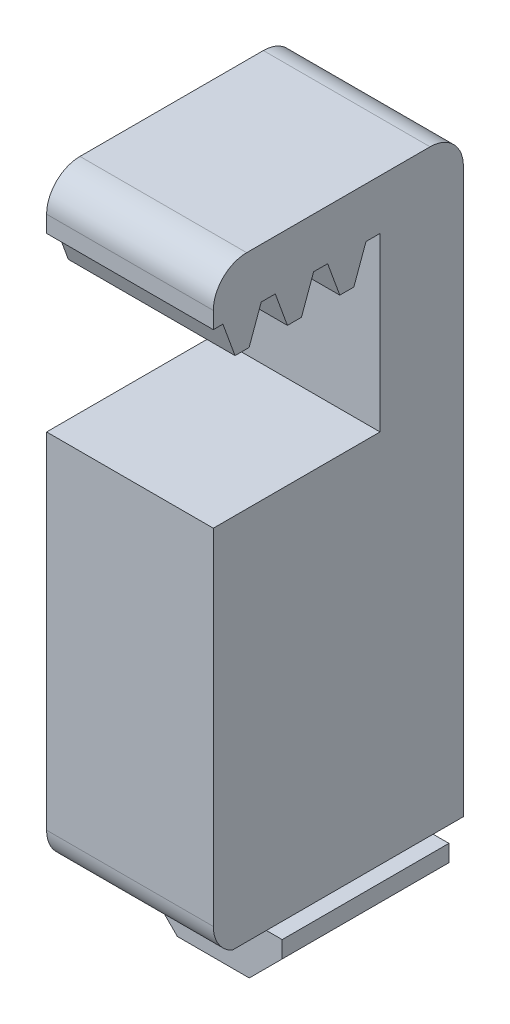
SolidWorks part; units mm, degrees
material "PLA Grey"
ref_plane "Front Plane" through (0, 0, 0) normal (0, 0, 1) x (1, 0, 0)
ref_plane "Top Plane" through (0, 0, 0) normal (0, 1, 0) x (1, 0, 0)
ref_plane "Right Plane" through (0, 0, 0) normal (1, 0, 0) x (0, 0, -1)
sketch "Sketch1" plane through (0, 0, 0) normal (1, 0, 0) x (0, 0, -1)
  line L0 (6.35, 0) -> (6.35, -6.096)
  line L1 (0, 45.72) -> (12.7, 45.72)
  line L2 (0, 45.72) -> (0, 39.37)
  line L3 (0, 39.37) -> (12.7, 39.37)
  line L5 (12.7, 45.72) -> (19.05, 45.72)
  line L6 (12.7, 39.37) -> (12.7, 29.21)
  line L7 (6.35, -6.096) -> (19.05, -6.096)
  line L8 (19.05, 45.72) -> (19.05, -6.096)
  line L9 (12.7, 29.21) -> (0, 29.21)
  line L11 (6.35, 0) -> (0, 0)
  line L12 (0, 29.21) -> (0, 0)
  line L13 (12.7, 29.21) -> (-1206.5, 29.21) construction
  dimension "D1" = 6.35
  dimension "D2" = 12.7
  dimension "D3" = 10.16
  dimension "D4" = 6.35
  dimension "D5" = 12.7
  dimension "D6" = 6.096
extrude "Boss-Extrude1" add sketch "Sketch1" along normal mid plane 12.7
sketch "Sketch2" plane through (6.35, 0, 0) normal (1, 0, 0) x (0, 0, -1)
  line L0 (3.6499, 41.91) -> (4.7203, 41.91) construction
  line L1 (5.6948, 39.2327) -> (4.7203, 41.91) construction
  line L2 (6.4261, 39.0652) -> (5.934, 39.0652) construction
  line L3 (7.6397, 41.91) -> (6.6653, 39.2327) construction
  line L4 (7.6397, 41.91) -> (8.7102, 41.91) construction
  line L5 (9.6846, 39.2327) -> (8.7102, 41.91) construction
  line L6 (10.4159, 39.0652) -> (9.9238, 39.0652) construction
  line L7 (11.6296, 41.91) -> (10.6551, 39.2327) construction
  line L8 (11.6296, 41.91) -> (12.7, 41.91) construction
  line L9 (3.6499, 41.91) -> (4.7203, 41.91)
  line L10 (5.6948, 39.2327) -> (4.7203, 41.91)
  line L11 (6.4261, 39.0652) -> (5.934, 39.0652)
  line L12 (7.6397, 41.91) -> (6.6653, 39.2327)
  line L13 (7.6397, 41.91) -> (8.7102, 41.91)
  line L14 (9.6846, 39.2327) -> (8.7102, 41.91)
  line L15 (10.4159, 39.0652) -> (9.9238, 39.0652)
  line L16 (11.6296, 41.91) -> (10.6551, 39.2327)
  line L17 (11.6296, 41.91) -> (12.7, 41.91)
  line L18 (12.7, 41.91) -> (12.7, 29.21)
  line L19 (12.7, 39.37) -> (12.7, 29.21) construction
  line L20 (12.7, 29.21) -> (3.6499, 29.21)
  line L21 (3.6499, 29.21) -> (3.6499, 41.91)
  line L22 (12.7, 29.21) -> (0, 29.21) construction
  arc A0 (5.6948, 39.2327) -> (5.934, 39.0652) centre (5.934, 39.3198) ccw construction
  arc A1 (6.4261, 39.0652) -> (6.6653, 39.2327) centre (6.4261, 39.3198) ccw construction
  arc A2 (9.6846, 39.2327) -> (9.9238, 39.0652) centre (9.9238, 39.3198) ccw construction
  arc A3 (10.4159, 39.0652) -> (10.6551, 39.2327) centre (10.4159, 39.3198) ccw construction
  arc A4 (5.6948, 39.2327) -> (5.934, 39.0652) centre (5.934, 39.3198) ccw
  arc A5 (6.4261, 39.0652) -> (6.6653, 39.2327) centre (6.4261, 39.3198) ccw
  arc A6 (9.6846, 39.2327) -> (9.9238, 39.0652) centre (9.9238, 39.3198) ccw
  arc A7 (10.4159, 39.0652) -> (10.6551, 39.2327) centre (10.4159, 39.3198) ccw
extrude "Cut-Extrude1" cut sketch "Sketch2" against normal through all
pattern_linear "LPattern1" count 10 spacing 3.9898 along (0, 0, 1) of "Cut-Extrude1"
sketch "Sketch3" plane through (0, 0, -19.05) normal (0, 0, -1) x (-1, 0, 0)
  line L0 (-6.35, -6.096) -> (-2.8393, -6.1)
  line L1 (2.8393, -6.1) -> (5.5, -3.4393) construction
  line L2 (5.5, -3.4393) -> (5.5, -1.8) construction
  line L3 (5.5, -1.8) -> (3.125, -1.8) construction
  line L4 (3.125, -1.8) -> (3.125, -1.455) construction
  line L5 (3.125, -1.455) -> (4.58, 0) construction
  line L6 (15.42, 0) -> (4.58, 0) construction
  line L7 (-4.58, 0) -> (-9.5, 0) construction
  line L8 (-3.125, -1.455) -> (-4.58, 0) construction
  line L9 (-3.125, -1.8) -> (-3.125, -1.455) construction
  line L10 (-5.5, -1.8) -> (-3.125, -1.8) construction
  line L11 (-5.5, -3.4393) -> (-5.5, -1.8) construction
  line L12 (-2.8393, -6.1) -> (-5.5, -3.4393) construction
  line L13 (2.8393, -6.1) -> (6.35, -6.096)
  line L15 (2.8393, -6.1) -> (5.5, -3.4393)
  line L16 (5.5, -3.4393) -> (5.5, -1.8)
  line L17 (5.5, -1.8) -> (3.125, -1.8)
  line L18 (3.125, -1.8) -> (3.125, -1.455)
  line L19 (3.125, -1.455) -> (4.58, 0)
  line L20 (15.42, 0) -> (4.58, 0)
  line L21 (-4.58, 0) -> (-9.5, 0)
  line L22 (-3.125, -1.455) -> (-4.58, 0)
  line L23 (-3.125, -1.8) -> (-3.125, -1.455)
  line L24 (-5.5, -1.8) -> (-3.125, -1.8)
  line L25 (-5.5, -3.4393) -> (-5.5, -1.8)
  line L26 (-2.8393, -6.1) -> (-5.5, -3.4393)
  line L29 (-9.5, 0) -> (-6.35, -6.096)
  line L32 (6.35, -6.096) -> (15.42, 0)
extrude "Cut-Extrude2" cut sketch "Sketch3" against normal through all
fillet "Fillet1" radius 2.54 3 edges at (0, 0, 0) (0, 45.72, 0) (0, 45.72, -19.05)
sketch "Sketch5" plane through (0, 0, -19.05) normal (0, 0, -1) x (-1, 0, 0)
  line L0 (6.35, 0) -> (4.58, 0) construction
  line L1 (4.58, 0) -> (3.125, -1.455) construction
  line L2 (3.125, -1.455) -> (3.125, -1.8) construction
  line L3 (3.125, -1.8) -> (5.5, -1.8) construction
  line L4 (5.5, -1.8) -> (5.5, -3.4393) construction
  line L5 (5.5, -3.4393) -> (2.8433, -6.096) construction
  line L6 (-2.8433, -6.096) -> (2.8433, -6.096) construction
  line L7 (-2.8433, -6.096) -> (-5.5, -3.4393) construction
  line L8 (-5.5, -3.4393) -> (-5.5, -1.8) construction
  line L9 (-5.5, -1.8) -> (-3.125, -1.8) construction
  line L10 (-3.125, -1.8) -> (-3.125, -1.455) construction
  line L11 (-3.125, -1.455) -> (-4.58, 0) construction
  line L12 (-4.58, 0) -> (-6.35, 0) construction
  line L13 (6.35, 0) -> (4.58, 0)
  line L14 (4.58, 0) -> (3.125, -1.455)
  line L15 (3.125, -1.455) -> (3.125, -1.8)
  line L16 (3.125, -1.8) -> (5.5, -1.8)
  line L17 (5.5, -1.8) -> (5.5, -3.4393)
  line L18 (5.5, -3.4393) -> (2.8433, -6.096)
  line L19 (-2.8433, -6.096) -> (2.8433, -6.096)
  line L20 (-2.8433, -6.096) -> (-5.5, -3.4393)
  line L21 (-5.5, -3.4393) -> (-5.5, -1.8)
  line L22 (-5.5, -1.8) -> (-3.125, -1.8)
  line L23 (-3.125, -1.8) -> (-3.125, -1.455)
  line L24 (-3.125, -1.455) -> (-4.58, 0)
  line L25 (-4.58, 0) -> (-6.35, 0)
  line L26 (6.35, 0.254) -> (4.4748, 0.254)
  line L27 (4.4748, 0.254) -> (2.871, -1.3498)
  line L28 (2.871, -1.3498) -> (2.871, -2.054)
  line L29 (2.871, -2.054) -> (5.246, -2.054)
  line L30 (5.246, -2.054) -> (5.246, -3.3341)
  line L31 (5.246, -3.3341) -> (2.7381, -5.842)
  line L32 (-2.7381, -5.842) -> (2.7381, -5.842)
  line L33 (-2.7381, -5.842) -> (-5.246, -3.3341)
  line L34 (-5.246, -3.3341) -> (-5.246, -2.054)
  line L35 (-5.246, -2.054) -> (-2.871, -2.054)
  line L36 (-2.871, -2.054) -> (-2.871, -1.3498)
  line L37 (-2.871, -1.3498) -> (-4.4748, 0.254)
  line L38 (-4.4748, 0.254) -> (-6.35, 0.254)
  line L39 (6.35, 0) -> (6.35, 0.254)
  line L40 (-6.35, 0) -> (-6.35, 0.254)
  dimension "D1" = 0.254
extrude "Cut-Extrude3" cut sketch "Sketch5" against normal through all
sketch "Sketch6" plane through (6.35, 0, 0) normal (1, 0, 0) x (0, 0, -1)
  line L0 (12.7, 41.91) -> (12.7, 29.21) construction
  line L1 (0, 29.21) -> (12.7, 29.21)
  line L2 (0, 29.21) -> (0, 28.8131)
  line L3 (0, 28.8131) -> (12.7, 28.8131)
  line L4 (12.7, 29.21) -> (12.7, 28.8131)
  dimension "D1" = 0.3969
extrude "Cut-Extrude4" cut sketch "Sketch6" against normal through all
sketch "Sketch7" [suppressed] plane through (6.35, 0, 0) normal (1, 0, 0) x (0, 0, -1)
  line L0 (19.05, 0.1984) -> (19.05, 42.926) construction
  line L1 (0, 28.8131) -> (19.05, 28.8131)
  line L2 (0, 28.8131) -> (0, 45.466)
  line L3 (0, 45.466) -> (19.05, 45.466)
  line L4 (19.05, 28.8131) -> (19.05, 45.466)
  line L5 (0, 28.8131) -> (19.05, 45.466) construction
  line L6 (0, 45.466) -> (19.05, 28.8131) construction
  line L7 (16.51, 45.466) -> (2.54, 45.466) construction
  point P4 (9.525, 37.1396)
extrude "Cut-Extrude5" [suppressed] cut sketch "Sketch7" against normal through all and the other way through all
